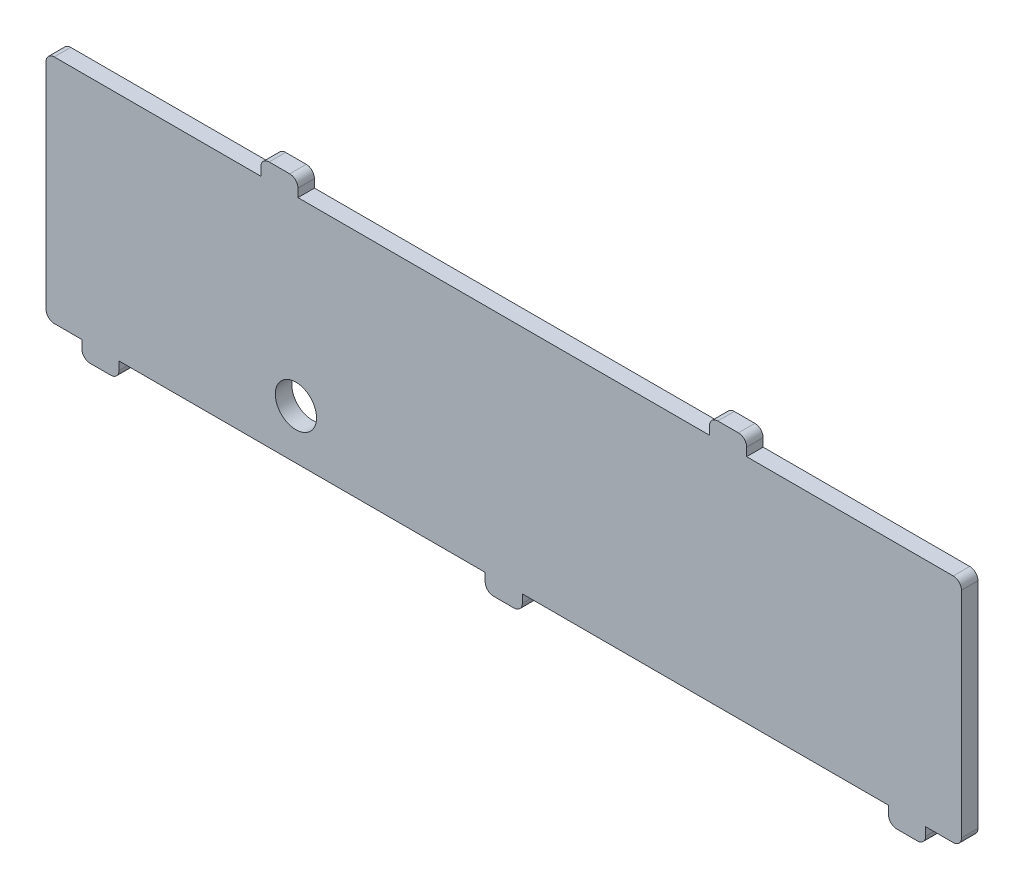
SolidWorks part; units mm, degrees
ref_plane "前基準面" through (0, 0, 0) normal (0, 0, 1) x (1, 0, 0)
ref_plane "上基準面" through (0, 0, 0) normal (0, 1, 0) x (1, 0, 0)
ref_plane "右基準面" through (0, 0, 0) normal (1, 0, 0) x (0, 0, -1)
sketch "Sketch1" plane through (0, 0, 0) normal (0, 0, 1) x (1, 0, 0)
  line L0 (0, 0) -> (0, -31.2064) construction
  line L1 (-55.5, 14) -> (55.5, 14)
  line L2 (-55.5, 14) -> (-55.5, -14)
  line L3 (-55.5, -14) -> (55.5, -14)
  line L4 (55.5, 14) -> (55.5, -14)
  line L5 (-55.5, 14) -> (55.5, -14) construction
  line L6 (-55.5, -14) -> (55.5, 14) construction
  line L7 (0, -31.2064) -> (0, 29.4941) construction
  line L8 (-2.25, -14) -> (2.25, -16) construction
  line L9 (-2.25, -14) -> (2.25, -14)
  line L10 (-2.25, -14) -> (-2.25, -16)
  line L11 (-2.25, -16) -> (2.25, -16)
  line L12 (2.25, -14) -> (2.25, -16)
  line L13 (-2.25, -16) -> (2.25, -14) construction
  line L14 (-51.15, -14) -> (-46.65, -16) construction
  line L15 (-51.15, -14) -> (-46.65, -14)
  line L16 (-51.15, -14) -> (-51.15, -16)
  line L17 (-51.15, -16) -> (-46.65, -16)
  line L18 (-46.65, -14) -> (-46.65, -16)
  line L19 (-46.65, -14) -> (-51.15, -16) construction
  line L20 (51.15, -16) -> (46.65, -16)
  line L21 (46.65, -14) -> (46.65, -16)
  line L22 (51.15, -14) -> (46.65, -14)
  line L23 (51.15, -14) -> (51.15, -16)
  line L24 (-48.9, -15) -> (-48.9, 18.4346) construction
  line L25 (0, -15.6032) -> (0, 17.9346) construction
  line L26 (46.65, -14) -> (51.15, -16) construction
  line L27 (51.15, -14) -> (46.65, -16) construction
  line L28 (-29.45, 16) -> (-24.95, 14) construction
  line L29 (-29.45, 14) -> (-24.95, 14)
  line L30 (-29.45, 14) -> (-29.45, 16)
  line L31 (-29.45, 16) -> (-24.95, 16)
  line L32 (-24.95, 14) -> (-24.95, 16)
  line L33 (-24.95, 16) -> (-29.45, 14) construction
  line L34 (29.45, 16) -> (24.95, 16)
  line L35 (24.95, 14) -> (24.95, 16)
  line L36 (29.45, 14) -> (24.95, 14)
  line L37 (29.45, 14) -> (29.45, 16)
  point P0 (0, 0)
  point P13 (0, -15)
  point P32 (-27.2, 15)
  dimension "D1" = 28
  dimension "D2" = 111
  dimension "D3" = 2
  dimension "D4" = 4.5
  dimension "D5" = 2
  dimension "D6" = 4.5
  dimension "D7" = 48.9
  dimension "D8" = 2
  dimension "D9" = 4.5
  dimension "D10" = 27.2
extrude "Boss-Extrude1" add sketch "Sketch1" along normal mid plane 2 contours L4 L1 L2 L3 | L12 L3 L10 L11 | L1 L37 L34 L35 | L1 L32 L31 L30 | L18 L17 L16 L15 | L23 L20 L21 L22 region at (0, 0, 0) region at (-27.2, 15, 0) region at (27.2, 15, 0) region at (0, -15, 0)
fillet "Fillet1" radius 1 14 edges at (-55.5, 14, 0) (-55.5, -14, 0) (-46.65, -16, 0) (-51.15, -16, 0) (2.25, -16, 0) (-2.25, -16, 0) (46.65, -16, 0) (51.15, -16, 0) (55.5, -14, 0) (55.5, 14, 0) (29.45, 16, 0) (24.95, 16, 0) (-24.95, 16, 0) (-29.45, 16, 0)
sketch "Sketch3" plane through (0, 0, 1) normal (0, 0, 1) x (1, 0, 0)
  line L0 (-25.2, -0.6049) -> (-25.2, -16) construction
  line L1 (-60.55, -16) -> (60.45, -16) construction
  line L2 (-55.6, 13) -> (-55.6, -13) construction
  circle A0 centre (-25.2, -8) radius 2.5
  dimension "D1" = 5
  dimension "D2" = 8
  dimension "D3" = 30.4
extrude "Cut-Extrude1" cut sketch "Sketch3" against normal up to next
